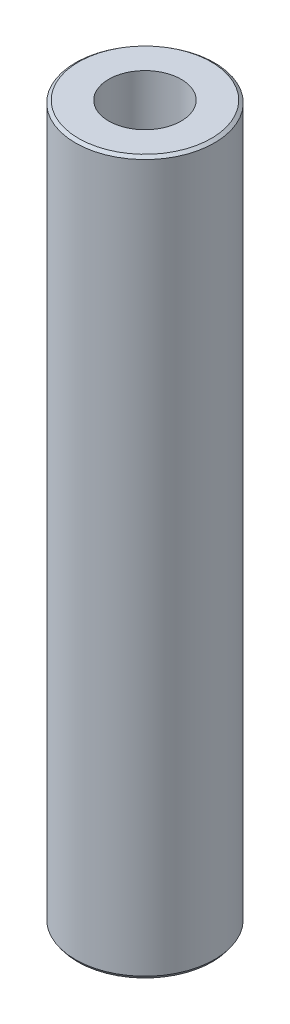
SolidWorks part; units mm, degrees
ref_plane "Front Plane" through (0, 0, 0) normal (0, 0, 1) x (1, 0, 0)
ref_plane "Top Plane" through (0, 0, 0) normal (0, 1, 0) x (1, 0, 0)
ref_plane "Right Plane" through (0, 0, 0) normal (1, 0, 0) x (0, 0, -1)
sketch "Sketch1" plane through (0, 0, 0) normal (0, 1, 0) x (1, 0, 0)
  circle A0 centre (0, 0) radius 12.5
  dimension "SHAFT_OD" = 25
extrude "Boss-Extrude1" add sketch "Sketch1" along normal blind 128.1699
sketch "Sketch2" plane through (0, 0, 0) normal (0, 1, 0) x (1, 0, 0)
  circle A0 centre (0, 0) radius 6.5183
  dimension "BORE_D" = 13.0366
extrude "Cut-Extrude1" cut sketch "Sketch2" along normal through all
chamfer "Chamfer1" distance 0.4172 angle 53.869 2 edges at (0, 128.1699, 12.5) (0, 0, 12.5) first distance on face at (0, 128.1699, 12.5) first distance on face at (0, 0, 6.5183)
